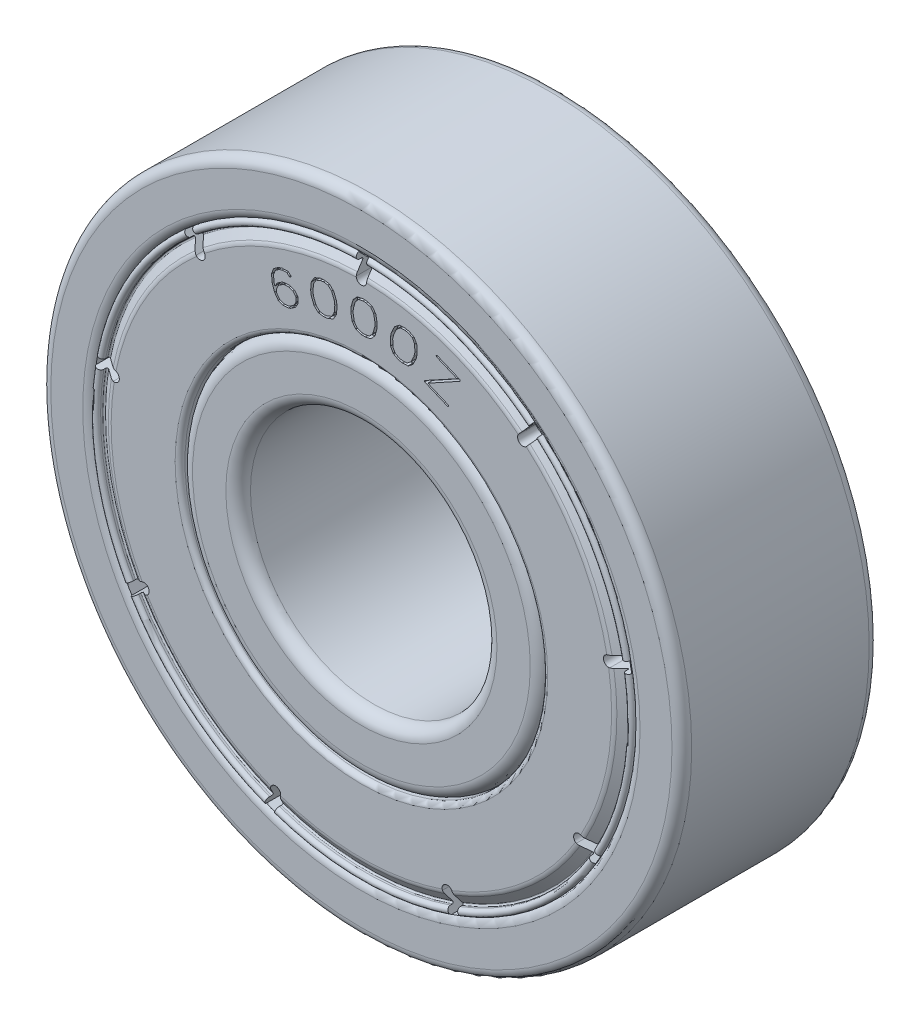
SolidWorks part; units mm, degrees
other "ID"
other "OD"
ref_plane "Front Plane" through (0, 0, 0) normal (0, 0, 1) x (1, 0, 0)
ref_plane "Top Plane" through (0, 0, 0) normal (0, 1, 0) x (1, 0, 0)
ref_plane "Right Plane" through (0, 0, 0) normal (1, 0, 0) x (0, 0, -1)
sketch "Sketch1" plane through (0, 0, 0) normal (0, 0, 1) x (1, 0, 0)
  circle A0 centre (0, 0) radius 13
  circle A1 centre (0, 0) radius 5
  circle A2 centre (0, 0) radius 7.35
  circle A3 centre (0, 0) radius 11
  dimension "D1" = 26
  dimension "D2" = 10
  dimension "D3" = 14.7
  dimension "D4" = 22
extrude "Rings" add sketch "Sketch1" against normal blind 8 contours A0 | A3 | A2 | A1
sketch "Sketch3" plane through (0, 0, 0) normal (0, 1, 0) x (1, 0, 0)
  line L0 (0, 0) -> (0, 8) construction
  line L1 (13, 8) -> (-13, 8) construction
ref_axis "Axis1" through (0, 0, -8) along (0, 0, 1)
fillet "Fillet2" radius 0.5 4 edges at (5, 0, -8) (7.35, 0, -8) (5, 0, 0) (7.35, 0, 0)
sketch "Sketch5" plane through (0, 0, 0) normal (0, 1, 0) x (1, 0, 0)
  line L0 (-13, 0) -> (13, 0) construction
  line L4 (7.5567, 0) -> (10.151, 0)
  line L5 (10.7201, 0.1407) -> (10.7201, 0.2218)
  line L7 (7.3567, 0.2) -> (7.3567, 4)
  line L8 (11, 0.1407) -> (11, 4)
  line L11 (10.6427, 0.2636) -> (10.3154, 0.0491)
  line L15 (7.3567, 4) -> (11, 4)
  arc A0 (11, 0.1407) -> (10.7201, 0.1407) centre (10.8601, 0.1407) cw
  arc A1 (7.3567, 0.2) -> (7.5567, 0) centre (7.5567, 0.2) ccw
  arc A2 (10.6427, 0.2636) -> (10.7201, 0.2218) centre (10.6701, 0.2218) cw
  arc A3 (10.151, 0) -> (10.3154, 0.0491) centre (10.151, 0.3) ccw
  point P16 (10.2405, 0)
  dimension "D1" = 0.2
  dimension "D2" = 0.05
  dimension "D3" = 4
  dimension "D4" = 0.3
revolve "Balls cover" add sketch "Sketch5" angle 360 about L0
ref_plane "Plane1" through (0, 0, -4) normal (0, 0, 1) x (1, 0, 0)
fillet "Fillet6" radius 0.4 4 edges at (11, 0, 0) (11, 0, -8) (13, 0, 0) (13, 0, -8)
mirror "Mirror12" about plane through (0, 0, -4) normal (0, 0, 1) of "Balls cover"
sketch "Sketch12" plane through (0, 0, 0) normal (0, 0, 1) x (1, 0, 0)
  line L0 (0, 11.1954) -> (0, 9.826) construction
  line L2 (0.2117, 10.9935) -> (0.2117, 10.1866)
  line L3 (-0.2117, 10.9935) -> (-0.2117, 10.1866)
  line L4 (-0.2117, 10.9935) -> (0.2117, 10.9935)
  arc A2 (-0.2117, 10.1866) -> (0.2117, 10.1866) centre (0, 10.1866) ccw
extrude "Slots" cut sketch "Sketch12" against normal through all contours L3 A2 L2 L4
pattern_circular "CirPattern6" count 9 over 360 of "Slots"
sketch "Sketch18" plane through (0, 0, 0) normal (0, 0, 1) x (1, 0, 0)
  arc A0 (-3.3727, 7.5839) -> (3.7653, 7.3968) centre (0, 0) cw construction
  text T0 "6000Z" font "SWSimp" height in points 5
extrude "Model No" cut sketch "Sketch18" against normal blind 0.2
